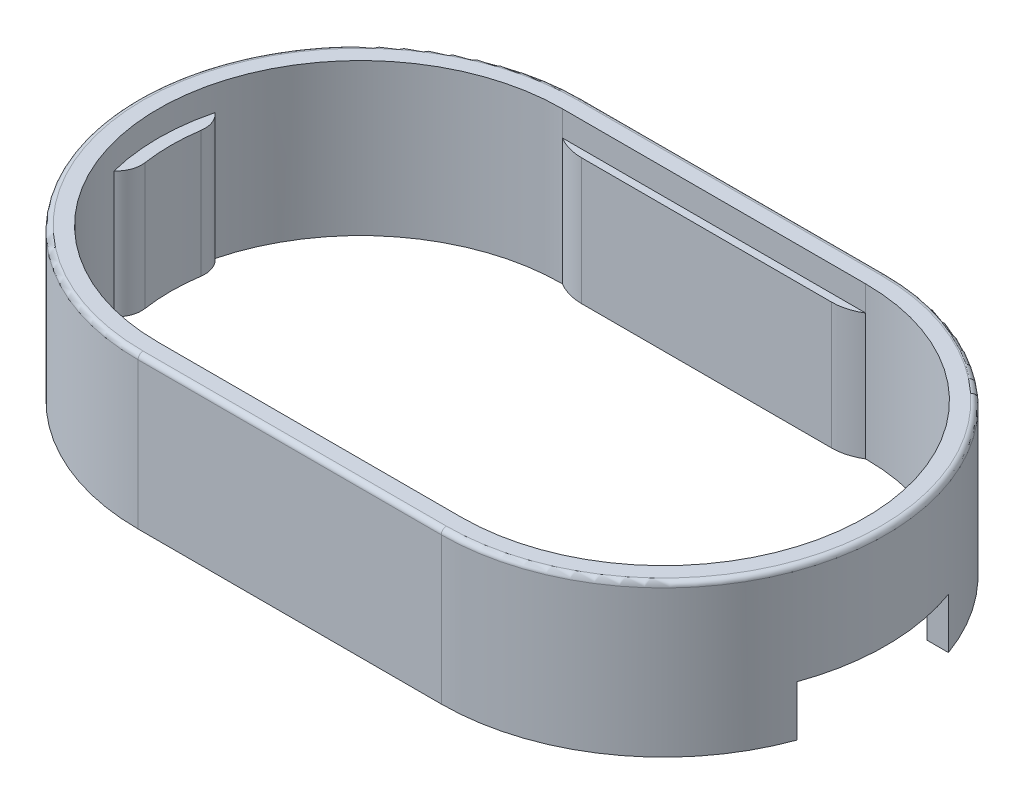
SolidWorks part; units mm, degrees
ref_plane "Front Plane" through (0, 0, 0) normal (0, 0, 1) x (1, 0, 0)
ref_plane "Top Plane" through (0, 0, 0) normal (0, 1, 0) x (1, 0, 0)
ref_plane "Right Plane" through (0, 0, 0) normal (1, 0, 0) x (0, 0, -1)
sketch "Sketch1" plane through (0, 0, 0) normal (0, 1, 0) x (1, 0, 0)
  line L0 (0, 0) -> (60, 0)
  line L1 (60, 88) -> (0, 88)
  arc A0 (60, 0) -> (60, 88) centre (60, 44) ccw
  arc A1 (0, 88) -> (0, 0) centre (0, 44) ccw
  dimension "D1" = 60
extrude "Boss-Extrude1" add sketch "Sketch1" along normal blind 30
shell "Shell1" thickness 4 removed face at (30, 0, -44) removed face at (30, 30, -44)
sketch "Sketch3" plane through (0, 0, 0) normal (0, -1, 0) x (1, 0, 0)
  line L0 (0, -4) -> (0, -5.5)
  line L1 (0, -5.5) -> (60, -5.5)
  line L2 (60, -5.5) -> (60, -4)
  line L3 (60, -4) -> (0, -4)
  dimension "D1" = 1.5
extrude "Boss-Extrude2" add sketch "Sketch3" against normal blind 25
sketch "Sketch5" plane through (0, 0, 0) normal (0, -1, 0) x (1, 0, 0)
  line L0 (0, -84) -> (0, -82.5)
  line L1 (0, -82.5) -> (60.0038, -82.5)
  line L2 (60.0038, -82.5) -> (60, -84)
  line L3 (60, -84) -> (0, -84)
extrude "Boss-Extrude3" add sketch "Sketch5" against normal blind 25
fillet "Fillet2" radius 10 4 edges at (60, 12.5, -5.5) (60.0038, 12.5, -82.5) (0, 12.5, -82.5) (0, 12.5, -5.5)
sketch "Sketch8" plane through (0, 0, 0) normal (0, -1, 0) x (1, 0, 0)
  line L0 (100, -44) -> (60, -44) construction
  line L1 (30, -5.5) -> (30, -82.5) construction
  line L2 (5.2678, -5.5) -> (54.7322, -5.5) construction
  line L3 (54.7322, -82.5) -> (5.2678, -82.5) construction
  line L4 (35.9573, -34) -> (113.0034, -34) construction
  line L5 (35.9573, -54) -> (113.0034, -54) construction
  line L6 (96.1421, -34) -> (98.7298, -34)
  line L7 (96.1421, -54) -> (98.7298, -54)
  line L8 (-36.1421, -54) -> (-38.7298, -54)
  line L9 (-36.1421, -34) -> (-38.7298, -34)
  arc A0 (60, -84) -> (60, -4) centre (60, -44) ccw construction
  arc A1 (96.1421, -54) -> (96.1421, -34) centre (60, -44) ccw
  arc A2 (98.7298, -54) -> (98.7298, -34) centre (60, -44) ccw
  arc A3 (-38.7298, -54) -> (-38.7298, -34) centre (0, -44) cw
  arc A4 (-36.1421, -54) -> (-36.1421, -34) centre (0, -44) cw
  dimension "D1" = 10
extrude "Boss-Extrude5" add sketch "Sketch8" against normal blind 25
fillet "Fillet5" radius 5 4 edges at (96.1421, 12.5, -34) (96.1421, 12.5, -54) (-36.1421, 12.5, -34) (-36.1421, 12.5, -54)
fillet "Fillet6" radius 1 4 edges at (30, 30, -88) (104, 30, -44) (30, 30, 0) (-44, 30, -44)
sketch "Sketch9" plane through (0, 0, 0) normal (0, -1, 0) x (1, 0, 0)
  line L0 (60, 0) -> (60, -88) construction
  line L1 (60, -44) -> (121.3555, -44) construction
  line L2 (110.7181, -59) -> (110.7181, -29)
  line L3 (110.7181, -29) -> (93.7181, -29)
  line L4 (93.7181, -29) -> (93.7181, -59)
  line L5 (110.7181, -59) -> (93.7181, -59)
  arc A0 (60, -88) -> (60, 0) centre (60, -44) ccw construction
  point P14 (93.7181, -44)
  point P15 (110.7181, -44)
  dimension "D1" = 15
  dimension "D2" = 17
extrude "Cut-Extrude1" cut sketch "Sketch9" against normal blind 10
